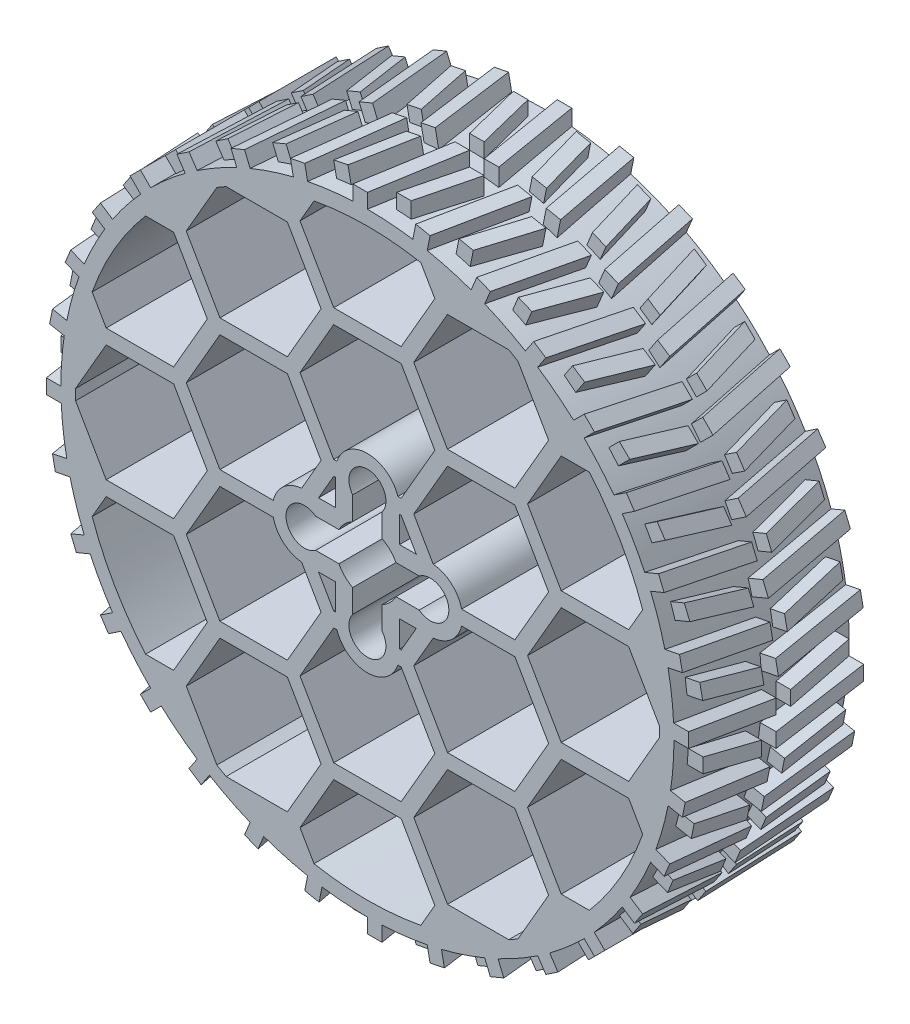
SolidWorks part; units mm, degrees
note: The reader was unsure of these and kept them because the rebuilt part matched: shared geometry of "Sketch1<4>", "Sketch1<6>".
ref_plane "Front Plane" through (0, 0, 0) normal (0, 0, 1) x (1, 0, 0)
ref_plane "Top Plane" through (0, 0, 0) normal (0, 1, 0) x (1, 0, 0)
ref_plane "Right Plane" through (0, 0, 0) normal (1, 0, 0) x (0, 0, -1)
sketch "Sketch1" plane through (0, 0, 0) normal (0, 0, 1) x (1, 0, 0)
  line L0 (-23.094, 45) -> (-11.547, 25)
  line L2 (-11.547, -20) -> (-11, -20)
  line L3 (11.547, -20) -> (16.7432, -11)
  line L4 (17.3205, 10) -> (17.2484, 10.1249)
  line L5 (11.547, 20) -> (11, 20)
  line L6 (-11.547, 20) -> (-16.7432, 11)
  line L7 (-11.547, 25) -> (-10.4443, 25)
  line L8 (11.547, 25) -> (23.094, 45)
  line L9 (23.094, 45) -> (11.547, 65)
  line L10 (11.547, 65) -> (-11.547, 65)
  line L11 (-11.547, 65) -> (-23.094, 45)
  line L12 (-23.094, 90) -> (-11.547, 70)
  line L13 (-11.547, 70) -> (11.547, 70)
  line L14 (11.547, 70) -> (23.094, 90)
  line L15 (23.094, 90) -> (18.2949, 98.3122)
  line L17 (-18.2949, 98.3122) -> (-23.094, 90)
  line L18 (-23.094, -45) -> (-11.547, -65)
  line L19 (-11.547, -65) -> (11.547, -65)
  line L20 (11.547, -65) -> (23.094, -45)
  line L21 (23.094, -45) -> (11.547, -25)
  line L22 (11.547, -25) -> (10.4443, -25)
  line L23 (-11.547, -25) -> (-23.094, -45)
  line L24 (-23.094, -90) -> (-18.2949, -98.3122)
  line L26 (18.2949, -98.3122) -> (23.094, -90)
  line L27 (23.094, -90) -> (11.547, -70)
  line L28 (11.547, -70) -> (-11.547, -70)
  line L29 (-11.547, -70) -> (-23.094, -90)
  line L30 (15.8771, 22.5) -> (22.5427, 10.9549)
  line L31 (32.2601, 2.5) -> (50.5181, 2.5)
  line L32 (50.5181, 2.5) -> (62.0652, 22.5)
  line L33 (62.0652, 22.5) -> (50.5181, 42.5)
  line L34 (50.5181, 42.5) -> (27.4241, 42.5)
  line L35 (27.4241, 42.5) -> (15.8771, 22.5)
  line L36 (22.5427, -10.9549) -> (15.8771, -22.5)
  line L37 (15.8771, -22.5) -> (27.4241, -42.5)
  line L38 (27.4241, -42.5) -> (50.5181, -42.5)
  line L39 (50.5181, -42.5) -> (62.0652, -22.5)
  line L40 (62.0652, -22.5) -> (50.5181, -2.5)
  line L41 (50.5181, -2.5) -> (32.2601, -2.5)
  line L42 (11.547, -25) -> (10.4443, -25)
  line L43 (-11.547, -25) -> (-23.094, -45)
  line L44 (-23.094, -45) -> (-11.547, -65)
  line L45 (-11.547, -65) -> (11.547, -65)
  line L46 (11.547, -65) -> (23.094, -45)
  line L47 (23.094, -45) -> (11.547, -25)
  line L48 (-15.8771, -22.5) -> (-22.5427, -10.9549)
  line L49 (-32.2601, -2.5) -> (-50.5181, -2.5)
  line L50 (-50.5181, -2.5) -> (-62.0652, -22.5)
  line L51 (-62.0652, -22.5) -> (-50.5181, -42.5)
  line L52 (-50.5181, -42.5) -> (-27.4241, -42.5)
  line L53 (-27.4241, -42.5) -> (-15.8771, -22.5)
  line L54 (-22.5427, 10.9549) -> (-15.8771, 22.5)
  line L55 (-15.8771, 22.5) -> (-27.4241, 42.5)
  line L56 (-27.4241, 42.5) -> (-50.5181, 42.5)
  line L57 (-50.5181, 42.5) -> (-62.0652, 22.5)
  line L58 (-62.0652, 22.5) -> (-50.5181, 2.5)
  line L59 (-50.5181, 2.5) -> (-32.2601, 2.5)
  line L60 (-11.547, 25) -> (-10.4443, 25)
  line L61 (11.547, 25) -> (23.094, 45)
  line L62 (23.094, 45) -> (11.547, 65)
  line L63 (11.547, 65) -> (-11.547, 65)
  line L64 (-11.547, 65) -> (-23.094, 45)
  line L65 (-23.094, 45) -> (-11.547, 25)
  line L66 (-27.4241, 47.5) -> (-15.8771, 67.5)
  line L67 (-15.8771, 67.5) -> (-27.4241, 87.5)
  line L68 (-27.4241, 87.5) -> (-48.4123, 87.5)
  line L69 (-51.5711, 85.6763) -> (-62.0652, 67.5)
  line L70 (-62.0652, 67.5) -> (-50.5181, 47.5)
  line L71 (-50.5181, 47.5) -> (-27.4241, 47.5)
  line L72 (-15.8771, -67.5) -> (-27.4241, -47.5)
  line L73 (-27.4241, -47.5) -> (-50.5181, -47.5)
  line L74 (-50.5181, -47.5) -> (-62.0652, -67.5)
  line L75 (-62.0652, -67.5) -> (-51.5711, -85.6763)
  line L76 (-48.4123, -87.5) -> (-27.4241, -87.5)
  line L77 (-27.4241, -87.5) -> (-15.8771, -67.5)
  line L78 (-66.3953, 25) -> (-54.8483, 45)
  line L79 (-54.8483, 45) -> (-66.3953, 65)
  line L80 (-66.3953, 65) -> (-75.9934, 65)
  line L82 (-94.2884, 33.3122) -> (-89.4893, 25)
  line L83 (-89.4893, 25) -> (-66.3953, 25)
  line L84 (-66.3953, -20) -> (-54.8483, 0)
  line L85 (-54.8483, 0) -> (-66.3953, 20)
  line L86 (-66.3953, 20) -> (-89.4893, 20)
  line L87 (-89.4893, 20) -> (-99.9834, 1.8237)
  line L88 (-99.9834, -1.8237) -> (-89.4893, -20)
  line L89 (-89.4893, -20) -> (-66.3953, -20)
  line L90 (-66.3953, -65) -> (-54.8483, -45)
  line L91 (-54.8483, -45) -> (-66.3953, -25)
  line L92 (-66.3953, -25) -> (-89.4893, -25)
  line L93 (-89.4893, -25) -> (-94.2884, -33.3122)
  line L95 (-75.9934, -65) -> (-66.3953, -65)
  line L96 (15.8771, 67.5) -> (27.4241, 47.5)
  line L97 (27.4241, 47.5) -> (50.5181, 47.5)
  line L98 (50.5181, 47.5) -> (62.0652, 67.5)
  line L99 (62.0652, 67.5) -> (51.5711, 85.6763)
  line L100 (48.4123, 87.5) -> (27.4241, 87.5)
  line L101 (27.4241, 87.5) -> (15.8771, 67.5)
  line L102 (27.4241, -47.5) -> (15.8771, -67.5)
  line L103 (15.8771, -67.5) -> (27.4241, -87.5)
  line L104 (27.4241, -87.5) -> (48.4123, -87.5)
  line L105 (51.5711, -85.6763) -> (62.0652, -67.5)
  line L106 (62.0652, -67.5) -> (50.5181, -47.5)
  line L107 (50.5181, -47.5) -> (27.4241, -47.5)
  line L108 (66.3953, -25) -> (54.8483, -45)
  line L109 (54.8483, -45) -> (66.3953, -65)
  line L110 (66.3953, -65) -> (75.9934, -65)
  line L112 (94.2884, -33.3122) -> (89.4893, -25)
  line L113 (89.4893, -25) -> (66.3953, -25)
  line L114 (66.3953, 20) -> (54.8483, 0)
  line L115 (54.8483, 0) -> (66.3953, -20)
  line L116 (66.3953, -20) -> (89.4893, -20)
  line L117 (89.4893, -20) -> (99.9834, -1.8237)
  line L118 (99.9834, 1.8237) -> (89.4893, 20)
  line L119 (89.4893, 20) -> (66.3953, 20)
  line L120 (66.3953, 65) -> (54.8483, 45)
  line L121 (54.8483, 45) -> (66.3953, 25)
  line L122 (66.3953, 25) -> (89.4893, 25)
  line L123 (89.4893, 25) -> (94.2884, 33.3122)
  line L125 (75.9934, 65) -> (66.3953, 65)
  line L126 (-11.547, -110) -> (11.547, -110) [skipped]
  line L127 (89.4893, -65) -> (101.0363, -45) [skipped]
  line L128 (101.0363, 45) -> (89.4893, 65) [skipped]
  line L129 (11.547, 110) -> (-11.547, 110) [skipped]
  line L130 (-89.4893, 65) -> (-101.0363, 45) [skipped]
  line L131 (-101.0363, -45) -> (-89.4893, -65) [skipped]
  line L132 (11, -20) -> (11.547, -20)
  line L133 (-11, 20) -> (-11.547, 20)
  line L134 (-10.4443, -25) -> (-11.547, -25)
  line L135 (-10.4443, -25) -> (-11.547, -25)
  line L136 (10.4443, 25) -> (11.547, 25)
  line L137 (10.4443, 25) -> (11.547, 25)
  line L138 (-5.0583, 17.7275) -> (-5.0583, 9.768)
  line L139 (5.0583, 17.7275) -> (5.0583, 9.768)
  line L140 (17.7275, 5.0583) -> (9.768, 5.0583)
  line L141 (17.7275, -5.0583) -> (9.768, -5.0583)
  line L142 (5.0583, -17.7275) -> (5.0583, -9.768)
  line L143 (-5.0583, -17.7275) -> (-5.0583, -9.768)
  line L144 (-17.7275, -5.0583) -> (-9.768, -5.0583)
  line L145 (-17.7275, 5.0583) -> (-9.768, 5.0583)
  line L146 (-21.548, 11) -> (-11, 11)
  line L147 (-11, 21.548) -> (-11, 11)
  line L148 (16.7432, 11) -> (11.547, 20)
  line L149 (21.548, 11) -> (11, 11)
  line L150 (11, 21.548) -> (11, 11)
  line L151 (11, -21.548) -> (11, -11)
  line L152 (21.548, -11) -> (11, -11)
  line L153 (-21.548, -11) -> (-11, -11)
  line L154 (-11, -21.548) -> (-11, -11)
  line L155 (-16.7432, -11) -> (-11.547, -20)
  line L156 (-17.3205, -10) -> (-17.2484, -10.1249) [skipped]
  circle A0 centre (0, 0) radius 100
  arc A1 (9.768, 5.0583) -> (5.0583, 9.768) centre (0, 0) ccw
  circle A2 centre (0, 0) radius 105
  arc A3 (-9.768, -5.0583) -> (-5.0583, -9.768) centre (0, 0) ccw
  arc A5 (21.548, -11) -> (21.548, 11) centre (21.548, 0) ccw
  arc A6 (-11, -21.548) -> (11, -21.548) centre (0, -21.548) ccw
  arc A7 (-21.548, 11) -> (-21.548, -11) centre (-21.548, 0) ccw
  arc A8 (11, 21.548) -> (-11, 21.548) centre (0, 21.548) ccw
  arc A9 (-5.0583, 9.768) -> (-9.768, 5.0583) centre (0, 0) ccw
  arc A10 (5.0583, -9.768) -> (9.768, -5.0583) centre (0, 0) ccw
  arc A11 (17.2484, 10.1249) -> (17.2479, 10.1247) centre (21.548, 0) ccw
  arc A14 (17.3205, 10) -> (17.2479, 10.1247) centre (0, 0) ccw construction
  circle A15 centre (0, 21.548) radius 3.175
  circle A16 centre (21.548, 0) radius 3.175
  circle A17 centre (0, -21.548) radius 3.175
  circle A18 centre (-21.548, 0) radius 3.175
  circle A19 centre (0, 21.548) radius 6.339
  circle A20 centre (21.548, 0) radius 6.339
  circle A21 centre (0, -21.548) radius 6.339
  circle A22 centre (-21.548, 0) radius 6.339
  arc A25 (-18.426, 0.5775) -> (-18.426, -0.5775) centre (0, 0) ccw
  arc A26 (0.5775, 18.426) -> (-0.5775, 18.426) centre (0, 0) ccw
  point P72 (0, 0)
  point P162 (0, 0)
  point P195 (0, 0)
  point P203 (0, 0)
  point P221 (0, 0)
  point P237 (0, 0)
  dimension "D15" = 2
  dimension "D19" = 5
  dimension "D20" = 4
  dimension "D21" = 4
  dimension "D22" = 4
  dimension "D24" = 11
  dimension "D25" = 12.678
  dimension "D26" = 6.35
  dimension "D27" = 10.548
  dimension "D5" = 5
  dimension "D17" = 5
  dimension "D18" = 5
  dimension "D2" = 3
  dimension "D3" = 3
  dimension "D4" = 2
  dimension "D7" = 2
  dimension "D8" = 2
  dimension "D9" = 2
  dimension "D10" = 3
  dimension "D11" = 2
  dimension "D12" = 2
  dimension "D13" = 2
  dimension "D14" = 3
  dimension "D6" = 6
  dimension "D16" = 4
  dimension "D23" = 4
extrude "Boss-Extrude1" add sketch "Sketch1" along normal blind 60
extrude "Boss-Extrude2" add sketch "Sketch1<4>" along normal blind 10 contours A19 A15 | A20 A16 | A22 A18 | A21 A17
sketch "Sketch1<4>" plane through (0, 0, 0) normal (0, 0, 1) x (1, 0, 0) same geometry as "Sketch1"
extrude "Boss-Extrude4" add sketch "Sketch1<6>" along normal blind 30 contours A21 A17 | A22 A18 | A20 A16 | A19 A15
sketch "Sketch1<6>" plane through (0, 0, 0) normal (0, 0, 1) x (1, 0, 0) same geometry as "Sketch1"
ref_plane "Plane1" through (105, 0, 0) normal (1, 0, 0) x (0, 0, -1)
sketch "Sketch2" plane through (105, 0, 0) normal (1, 0, 0) x (0, 0, -1)
  line L0 (-60, 0) -> (0, 0)
  line L1 (-30, 0) -> (-30, -5)
  line L2 (-30, -5) -> (-60, 0)
  line L3 (-60, 0) -> (-60, 5)
  line L4 (-60, 105) -> (-60, -105) construction
  line L5 (-60, 5) -> (-30, 0)
  line L6 (-30, 0) -> (-25, 0)
  line L7 (-30, -10) -> (0, -5)
  line L8 (0, -105) -> (0, 105) construction
  line L9 (0, -5) -> (0, -10)
  line L10 (0, -10) -> (-30, -15)
  line L11 (-30, -15) -> (-30, -10)
  line L12 (-25, 0) -> (-25, -5)
  line L13 (0, 0) -> (-5, 0)
  line L14 (-5, 0) -> (-5, 5)
  line L15 (-5, 5) -> (-25, 0)
  line L16 (-5, 0) -> (-25, -5)
  line L17 (-55, -5) -> (-35, -10)
  line L19 (-55, -10) -> (-35, -15)
  line L20 (-35, -15) -> (-35, -10)
  line L21 (-55, -5) -> (-55, -10)
extrude "Boss-Extrude5" add sketch "Sketch2" along normal blind 5 and the other way blind 2 contours L5 L3 L0 | L2 L1 L0 | L14 L15 L0 | L16 L0 L12 | L17 L21 L19 L20 | L11 L10 L9 L7
pattern_circular "CirPattern1" count 32 over 360 about axis through (0, 0, 0) along (0, 0, 1) of "Boss-Extrude5"
